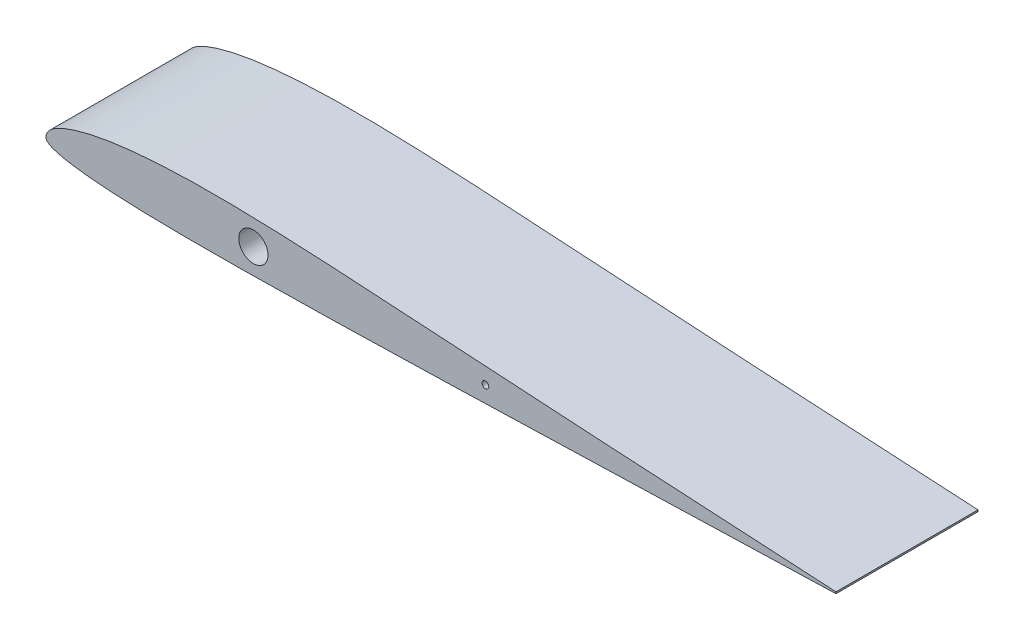
SolidWorks part; units mm, degrees
material "Polyurethane Foam Flexible"
ref_plane "Front Plane" through (0, 0, 0) normal (0, 0, 1) x (1, 0, 0)
ref_plane "Top Plane" through (0, 0, 0) normal (0, 1, 0) x (1, 0, 0)
ref_plane "Right Plane" through (0, 0, 0) normal (1, 0, 0) x (0, 0, -1)
curve "ht32-8-imported"
  spline degree 3 poles (203.2026, 0.2115, 0) (202.75, 0.2358, 0) (201.4822, 0.3036, 0) (199.2299, 0.4276, 0) (196.3046, 0.5865, 0) (192.9787, 0.7694, 0) (189.375, 0.9706, 0) (185.6129, 1.1785, 0) (181.7737, 1.3957, 0) (177.8996, 1.6147, 0) (174.01, 1.8354, 0) (170.1132, 2.0552, 0) (166.2133, 2.2775, 0) (162.3117, 2.4986, 0) (158.4107, 2.722, 0) (154.5106, 2.9441, 0) (150.6142, 3.1678, 0) (146.7204, 3.3936, 0) (142.8309, 3.617, 0) (138.944, 3.8454, 0) (135.0595, 4.0721, 0) (131.1775, 4.3012, 0) (127.2967, 4.5315, 0) (123.4189, 4.7649, 0) (119.5421, 5.0008, 0) (115.6675, 5.2398, 0) (111.7949, 5.4816, 0) (107.9236, 5.7247, 0) (104.0572, 5.9681, 0) (100.1894, 6.212, 0) (96.3188, 6.4543, 0) (92.4477, 6.6946, 0) (88.584, 6.9322, 0) (84.7415, 7.1637, 0) (80.9229, 7.3889, 0) (77.3978, 7.5906, 0) (74.5229, 7.7493, 0) (71.9946, 7.8843, 0) (69.1241, 8.0324, 0) (65.5083, 8.2076, 0) (61.4852, 8.3831, 0) (57.5218, 8.5328, 0) (53.6734, 8.652, 0) (49.9058, 8.739, 0) (46.181, 8.7912, 0) (42.491, 8.8047, 0) (38.8468, 8.7742, 0) (35.2596, 8.6962, 0) (31.7561, 8.5671, 0) (28.3661, 8.3856, 0) (25.1292, 8.152, 0) (22.0798, 7.8688, 0) (19.2587, 7.5428, 0) (16.7019, 7.1837, 0) (14.4336, 6.8058, 0) (12.4541, 6.4216, 0) (10.7471, 6.0418, 0) (9.283, 5.6741, 0) (8.0264, 5.3216, 0) (6.9394, 4.9844, 0) (5.9876, 4.6599, 0) (5.1429, 4.3427, 0) (4.3754, 4.0301, 0) (3.6577, 3.7081, 0) (2.9646, 3.3607, 0) (2.2868, 2.9708, 0) (1.6384, 2.5305, 0) (1.05, 2.0355, 0) (0.5511, 1.4823, 0) (0.1821, 0.8795, 0) (0.0202, 0.3651, 0) (-0.0065, -0.0193, 0) (0.0194, -0.3136, 0) (0.1268, -0.6144, 0) (0.297, -0.8546, 0) (0.4742, -1.036, 0) (0.6922, -1.2054, 0) (0.9846, -1.3848, 0) (1.3525, -1.5668, 0) (1.7794, -1.7448, 0) (2.2605, -1.9172, 0) (2.8067, -2.0876, 0) (3.4413, -2.2602, 0) (4.1881, -2.438, 0) (5.0669, -2.6215, 0) (6.0922, -2.8069, 0) (7.2766, -2.9931, 0) (8.6343, -3.178, 0) (10.1869, -3.3594, 0) (11.9608, -3.5369, 0) (13.9882, -3.7077, 0) (16.2949, -3.8689, 0) (18.8937, -4.0155, 0) (21.7662, -4.1437, 0) (24.8729, -4.2492, 0) (28.1584, -4.3297, 0) (31.5775, -4.3867, 0) (35.0914, -4.4207, 0) (38.6791, -4.4351, 0) (42.3216, -4.4311, 0) (46.0126, -4.4125, 0) (49.7579, -4.3795, 0) (53.5805, -4.3372, 0) (57.5149, -4.2842, 0) (61.5959, -4.2202, 0) (65.8841, -4.1445, 0) (69.584, -4.0721, 0) (72.8088, -4.005, 0) (75.5799, -3.9448, 0) (78.7708, -3.8727, 0) (82.2137, -3.7909, 0) (85.8123, -3.7021, 0) (89.4548, -3.6091, 0) (93.1502, -3.5116, 0) (96.8889, -3.4111, 0) (100.657, -3.3069, 0) (104.4397, -3.2018, 0) (108.2248, -3.0945, 0) (112.0082, -2.9863, 0) (115.791, -2.8766, 0) (119.5782, -2.7658, 0) (123.3765, -2.6523, 0) (127.1945, -2.5376, 0) (131.0416, -2.42, 0) (134.9198, -2.302, 0) (138.8194, -2.1823, 0) (142.7263, -2.0602, 0) (146.6334, -1.9373, 0) (150.5405, -1.8169, 0) (154.4476, -1.6935, 0) (158.3547, -1.5735, 0) (162.2615, -1.4515, 0) (166.1675, -1.3317, 0) (170.0718, -1.2089, 0) (173.9729, -1.0897, 0) (177.8669, -0.9678, 0) (181.7453, -0.8488, 0) (185.5889, -0.7312, 0) (189.3549, -0.6169, 0) (192.9626, -0.5096, 0) (196.292, -0.413, 0) (199.2203, -0.3248, 0) (201.4752, -0.2617, 0) (202.7443, -0.2247, 0) (203.1974, -0.2115, 0) knots 0 0 0 0 0.003316 0.009286 0.0165 0.024744 0.033651 0.0429 0.052304 0.061778 0.071282 0.080801 0.090326 0.099855 0.109385 0.118907 0.128429 0.137932 0.147436 0.156926 0.166412 0.175898 0.185369 0.194848 0.204314 0.213779 0.223243 0.232695 0.242152 0.25158 0.261042 0.270519 0.279949 0.289356 0.298677 0.307928 0.315183 0.319737 0.326448 0.336207 0.346216 0.355902 0.365219 0.374379 0.383467 0.392467 0.401369 0.410123 0.41871 0.427012 0.434953 0.442447 0.449411 0.455723 0.46133 0.466229 0.470471 0.47412 0.47727 0.480016 0.482444 0.484624 0.486615 0.488504 0.490376 0.492284 0.49422 0.496102 0.497896 0.499646 0.501237 0.501776 0.502457 0.503386 0.504071 0.504595 0.505236 0.506086 0.5071 0.508235 0.509467 0.510837 0.512419 0.514277 0.516452 0.518985 0.521897 0.525221 0.529007 0.53333 0.538261 0.543889 0.550243 0.557299 0.56492 0.57298 0.581338 0.589931 0.598683 0.607581 0.616575 0.625681 0.634977 0.644537 0.654462 0.664831 0.675908 0.681531 0.688425 0.696181 0.704877 0.713615 0.722511 0.731528 0.740655 0.749867 0.759101 0.768335 0.777565 0.786786 0.796016 0.805278 0.814581 0.823955 0.833431 0.842961 0.852492 0.862023 0.871554 0.881085 0.890615 0.900146 0.909675 0.9192 0.928718 0.938223 0.947696 0.9571 0.96635 0.975256 0.9835 0.990713 0.996685 1 1 1 1
sketch "Sketch3" plane through (0, 0, 0) normal (0, 0, 1) x (1, 0, 0)
  line L3 (203.2026, 0.2115) -> (203.1974, -0.2115)
  spline S0 degree 3 poles (334.6154, -3985.5649) (434.4726, 3.4305) (316.9129, -6.0481) (199.2299, 0.4276) (196.3046, 0.5865) (192.9787, 0.7694) (189.375, 0.9706) (185.6129, 1.1785) (181.7737, 1.3957) (177.8996, 1.6147) (174.01, 1.8354) (170.1132, 2.0552) (166.2133, 2.2775) (162.3117, 2.4986) (158.4107, 2.722) (154.5106, 2.9441) (150.6142, 3.1678) (146.7204, 3.3936) (142.8309, 3.617) (138.944, 3.8454) (135.0595, 4.0721) (131.1775, 4.3012) (127.2967, 4.5315) (123.4189, 4.7649) (119.5421, 5.0008) (115.6675, 5.2398) (111.7949, 5.4816) (107.9236, 5.7247) (104.0572, 5.9681) (100.1894, 6.212) (96.3188, 6.4543) (92.4477, 6.6946) (88.584, 6.9322) (84.7415, 7.1637) (80.9229, 7.3889) (77.3978, 7.5906) (74.5229, 7.7493) (71.9946, 7.8843) (69.1241, 8.0324) (65.5083, 8.2076) (61.4852, 8.3831) (57.5218, 8.5328) (53.6734, 8.652) (49.9058, 8.739) (46.181, 8.7912) (42.491, 8.8047) (38.8468, 8.7742) (35.2596, 8.6962) (31.7561, 8.5671) (28.3661, 8.3856) (25.1292, 8.152) (22.0798, 7.8688) (19.2587, 7.5428) (16.7019, 7.1837) (14.4336, 6.8058) (12.4541, 6.4216) (10.7471, 6.0418) (9.283, 5.6741) (8.0264, 5.3216) (6.9394, 4.9844) (5.9876, 4.6599) (5.1429, 4.3427) (4.3754, 4.0301) (3.6577, 3.7081) (2.9646, 3.3607) (2.2868, 2.9708) (1.6384, 2.5305) (1.05, 2.0355) (0.5511, 1.4823) (0.1821, 0.8795) (0.0202, 0.3651) (-0.0065, -0.0193) (0.0194, -0.3136) (0.1268, -0.6144) (0.297, -0.8546) (0.4742, -1.036) (0.6922, -1.2054) (0.9846, -1.3848) (1.3525, -1.5668) (1.7794, -1.7448) (2.2605, -1.9172) (2.8067, -2.0876) (3.4413, -2.2602) (4.1881, -2.438) (5.0669, -2.6215) (6.0922, -2.8069) (7.2766, -2.9931) (8.6343, -3.178) (10.1869, -3.3594) (11.9608, -3.5369) (13.9882, -3.7077) (16.2949, -3.8689) (18.8937, -4.0155) (21.7662, -4.1437) (24.8729, -4.2492) (28.1584, -4.3297) (31.5775, -4.3867) (35.0914, -4.4207) (38.6791, -4.4351) (42.3216, -4.4311) (46.0126, -4.4125) (49.7579, -4.3795) (53.5805, -4.3372) (57.5149, -4.2842) (61.5959, -4.2202) (65.8841, -4.1445) (69.584, -4.0721) (72.8088, -4.005) (75.5799, -3.9448) (78.7708, -3.8727) (82.2137, -3.7909) (85.8123, -3.7021) (89.4548, -3.6091) (93.1502, -3.5116) (96.8889, -3.4111) (100.657, -3.3069) (104.4397, -3.2018) (108.2248, -3.0945) (112.0082, -2.9863) (115.791, -2.8766) (119.5782, -2.7658) (123.3765, -2.6523) (127.1945, -2.5376) (131.0416, -2.42) (134.9198, -2.302) (138.8194, -2.1823) (142.7263, -2.0602) (146.6334, -1.9373) (150.5405, -1.8169) (154.4476, -1.6935) (158.3547, -1.5735) (162.2615, -1.4515) (166.1675, -1.3317) (170.0718, -1.2089) (173.9729, -1.0897) (177.8669, -0.9678) (181.7453, -0.8488) (185.5889, -0.7312) (189.3549, -0.6169) (192.9626, -0.5096) (196.292, -0.413) (199.2203, -0.3248) (326.9818, 3.2507) (453.3355, 21.4084) (694.2785, -3955.64) knots -0.845599 -0.845599 -0.845599 -0.845599 0.003316 0.009286 0.0165 0.024744 0.033651 0.0429 0.052304 0.061778 0.071282 0.080801 0.090326 0.099855 0.109385 0.118907 0.128429 0.137932 0.147436 0.156926 0.166412 0.175898 0.185369 0.194848 0.204314 0.213779 0.223243 0.232695 0.242152 0.25158 0.261042 0.270519 0.279949 0.289356 0.298677 0.307928 0.315183 0.319737 0.326448 0.336207 0.346216 0.355902 0.365219 0.374379 0.383467 0.392467 0.401369 0.410123 0.41871 0.427012 0.434953 0.442447 0.449411 0.455723 0.46133 0.466229 0.470471 0.47412 0.47727 0.480016 0.482444 0.484624 0.486615 0.488504 0.490376 0.492284 0.49422 0.496102 0.497896 0.499646 0.501237 0.501776 0.502457 0.503386 0.504071 0.504595 0.505236 0.506086 0.5071 0.508235 0.509467 0.510837 0.512419 0.514277 0.516452 0.518985 0.521897 0.525221 0.529007 0.53333 0.538261 0.543889 0.550243 0.557299 0.56492 0.57298 0.581338 0.589931 0.598683 0.607581 0.616575 0.625681 0.634977 0.644537 0.654462 0.664831 0.675908 0.681531 0.688425 0.696181 0.704877 0.713615 0.722511 0.731528 0.740655 0.749867 0.759101 0.768335 0.777565 0.786786 0.796016 0.805278 0.814581 0.823955 0.833431 0.842961 0.852492 0.862023 0.871554 0.881085 0.890615 0.900146 0.909675 0.9192 0.928718 0.938223 0.947696 0.9571 0.96635 0.975256 0.9835 0.990713 0.996685 1.918381 1.918381 1.918381 1.918381 only from (203.2026, 0.2115) to (203.1974, -0.2115) construction
  spline S1 degree 3 poles (203.2026, 0.2115) (202.75, 0.2358) (201.4822, 0.3036) (199.2299, 0.4276) (196.3046, 0.5865) (192.9787, 0.7694) (189.375, 0.9706) (185.6129, 1.1785) (181.7737, 1.3957) (177.8996, 1.6147) (174.01, 1.8354) (170.1132, 2.0552) (166.2133, 2.2775) (162.3117, 2.4986) (158.4107, 2.722) (154.5106, 2.9441) (150.6142, 3.1678) (146.7204, 3.3936) (142.8309, 3.617) (138.944, 3.8454) (135.0595, 4.0721) (131.1775, 4.3012) (127.2967, 4.5315) (123.4189, 4.7649) (119.5421, 5.0008) (115.6675, 5.2398) (111.7949, 5.4816) (107.9236, 5.7247) (104.0572, 5.9681) (100.1894, 6.212) (96.3188, 6.4543) (92.4477, 6.6946) (88.584, 6.9322) (84.7415, 7.1637) (80.9229, 7.3889) (77.3978, 7.5906) (74.5229, 7.7493) (71.9946, 7.8843) (69.1241, 8.0324) (65.5083, 8.2076) (61.4852, 8.3831) (57.5218, 8.5328) (53.6734, 8.652) (49.9058, 8.739) (46.181, 8.7912) (42.491, 8.8047) (38.8468, 8.7742) (35.2596, 8.6962) (31.7561, 8.5671) (28.3661, 8.3856) (25.1292, 8.152) (22.0798, 7.8688) (19.2587, 7.5428) (16.7019, 7.1837) (14.4336, 6.8058) (12.4541, 6.4216) (10.7471, 6.0418) (9.283, 5.6741) (8.0264, 5.3216) (6.9394, 4.9844) (5.9876, 4.6599) (5.1429, 4.3427) (4.3754, 4.0301) (3.6577, 3.7081) (2.9646, 3.3607) (2.2868, 2.9708) (1.6384, 2.5305) (1.05, 2.0355) (0.5511, 1.4823) (0.1821, 0.8795) (0.0202, 0.3651) (-0.0065, -0.0193) (0.0194, -0.3136) (0.1268, -0.6144) (0.297, -0.8546) (0.4742, -1.036) (0.6922, -1.2054) (0.9846, -1.3848) (1.3525, -1.5668) (1.7794, -1.7448) (2.2605, -1.9172) (2.8067, -2.0876) (3.4413, -2.2602) (4.1881, -2.438) (5.0669, -2.6215) (6.0922, -2.8069) (7.2766, -2.9931) (8.6343, -3.178) (10.1869, -3.3594) (11.9608, -3.5369) (13.9882, -3.7077) (16.2949, -3.8689) (18.8937, -4.0155) (21.7662, -4.1437) (24.8729, -4.2492) (28.1584, -4.3297) (31.5775, -4.3867) (35.0914, -4.4207) (38.6791, -4.4351) (42.3216, -4.4311) (46.0126, -4.4125) (49.7579, -4.3795) (53.5805, -4.3372) (57.5149, -4.2842) (61.5959, -4.2202) (65.8841, -4.1445) (69.584, -4.0721) (72.8088, -4.005) (75.5799, -3.9448) (78.7708, -3.8727) (82.2137, -3.7909) (85.8123, -3.7021) (89.4548, -3.6091) (93.1502, -3.5116) (96.8889, -3.4111) (100.657, -3.3069) (104.4397, -3.2018) (108.2248, -3.0945) (112.0082, -2.9863) (115.791, -2.8766) (119.5782, -2.7658) (123.3765, -2.6523) (127.1945, -2.5376) (131.0416, -2.42) (134.9198, -2.302) (138.8194, -2.1823) (142.7263, -2.0602) (146.6334, -1.9373) (150.5405, -1.8169) (154.4476, -1.6935) (158.3547, -1.5735) (162.2615, -1.4515) (166.1675, -1.3317) (170.0718, -1.2089) (173.9729, -1.0897) (177.8669, -0.9678) (181.7453, -0.8488) (185.5889, -0.7312) (189.3549, -0.6169) (192.9626, -0.5096) (196.292, -0.413) (199.2203, -0.3248) (201.4752, -0.2617) (202.7443, -0.2247) (203.1974, -0.2115) knots 0 0 0 0 0.003316 0.009286 0.0165 0.024744 0.033651 0.0429 0.052304 0.061778 0.071282 0.080801 0.090326 0.099855 0.109385 0.118907 0.128429 0.137932 0.147436 0.156926 0.166412 0.175898 0.185369 0.194848 0.204314 0.213779 0.223243 0.232695 0.242152 0.25158 0.261042 0.270519 0.279949 0.289356 0.298677 0.307928 0.315183 0.319737 0.326448 0.336207 0.346216 0.355902 0.365219 0.374379 0.383467 0.392467 0.401369 0.410123 0.41871 0.427012 0.434953 0.442447 0.449411 0.455723 0.46133 0.466229 0.470471 0.47412 0.47727 0.480016 0.482444 0.484624 0.486615 0.488504 0.490376 0.492284 0.49422 0.496102 0.497896 0.499646 0.501237 0.501776 0.502457 0.503386 0.504071 0.504595 0.505236 0.506086 0.5071 0.508235 0.509467 0.510837 0.512419 0.514277 0.516452 0.518985 0.521897 0.525221 0.529007 0.53333 0.538261 0.543889 0.550243 0.557299 0.56492 0.57298 0.581338 0.589931 0.598683 0.607581 0.616575 0.625681 0.634977 0.644537 0.654462 0.664831 0.675908 0.681531 0.688425 0.696181 0.704877 0.713615 0.722511 0.731528 0.740655 0.749867 0.759101 0.768335 0.777565 0.786786 0.796016 0.805278 0.814581 0.823955 0.833431 0.842961 0.852492 0.862023 0.871554 0.881085 0.890615 0.900146 0.909675 0.9192 0.928718 0.938223 0.947696 0.9571 0.96635 0.975256 0.9835 0.990713 0.996685 1 1 1 1
extrude "Airfoil" add sketch "Sketch3" along normal blind 36.5252
sketch "Sketch8" plane through (0, 0, 0) normal (0, 0, -1) x (-1, 0, 0)
  line L0 (0, 16.6795) -> (0, -1.637) construction
  line L2 (-53.34, 2.1587) -> (-53.34, 8.6559) construction
  line L3 (-53.34, 2.1587) -> (-53.34, -4.3386) construction
  circle A0 centre (-53.34, 2.1587) radius 3.7592
  spline S2 degree 3 poles (-203.2026, 0.2115) (-202.75, 0.2358) (-201.4822, 0.3036) (-199.2299, 0.4276) (-196.3046, 0.5865) (-192.9787, 0.7694) (-189.375, 0.9706) (-185.6129, 1.1785) (-181.7737, 1.3957) (-177.8996, 1.6147) (-174.01, 1.8354) (-170.1132, 2.0552) (-166.2133, 2.2775) (-162.3117, 2.4986) (-158.4107, 2.722) (-154.5106, 2.9441) (-150.6142, 3.1678) (-146.7204, 3.3936) (-142.8309, 3.617) (-138.944, 3.8454) (-135.0595, 4.0721) (-131.1775, 4.3012) (-127.2967, 4.5315) (-123.4189, 4.7649) (-119.5421, 5.0008) (-115.6675, 5.2398) (-111.7949, 5.4816) (-107.9236, 5.7247) (-104.0572, 5.9681) (-100.1894, 6.212) (-96.3188, 6.4543) (-92.4477, 6.6946) (-88.584, 6.9322) (-84.7415, 7.1637) (-80.9229, 7.3889) (-77.3978, 7.5906) (-74.5229, 7.7493) (-71.9946, 7.8843) (-69.1241, 8.0324) (-65.5083, 8.2076) (-61.4852, 8.3831) (-57.5218, 8.5328) (-53.6734, 8.652) (-49.9058, 8.739) (-46.181, 8.7912) (-42.491, 8.8047) (-38.8468, 8.7742) (-35.2596, 8.6962) (-31.7561, 8.5671) (-28.3661, 8.3856) (-25.1292, 8.152) (-22.0798, 7.8688) (-19.2587, 7.5428) (-16.7019, 7.1837) (-14.4336, 6.8058) (-12.4541, 6.4216) (-10.7471, 6.0418) (-9.283, 5.6741) (-8.0264, 5.3216) (-6.9394, 4.9844) (-5.9876, 4.6599) (-5.1429, 4.3427) (-4.3754, 4.0301) (-3.6577, 3.7081) (-2.9646, 3.3607) (-2.2868, 2.9708) (-1.6384, 2.5305) (-1.05, 2.0355) (-0.5511, 1.4823) (-0.1821, 0.8795) (-0.0202, 0.3651) (0.0065, -0.0193) (-0.0194, -0.3136) (-0.1268, -0.6144) (-0.297, -0.8546) (-0.4742, -1.036) (-0.6922, -1.2054) (-0.9846, -1.3848) (-1.3525, -1.5668) (-1.7794, -1.7448) (-2.2605, -1.9172) (-2.8067, -2.0876) (-3.4413, -2.2602) (-4.1881, -2.438) (-5.0669, -2.6215) (-6.0922, -2.8069) (-7.2766, -2.9931) (-8.6343, -3.178) (-10.1869, -3.3594) (-11.9608, -3.5369) (-13.9882, -3.7077) (-16.2949, -3.8689) (-18.8937, -4.0155) (-21.7662, -4.1437) (-24.8729, -4.2492) (-28.1584, -4.3297) (-31.5775, -4.3867) (-35.0914, -4.4207) (-38.6791, -4.4351) (-42.3216, -4.4311) (-46.0126, -4.4125) (-49.7579, -4.3795) (-53.5805, -4.3372) (-57.5149, -4.2842) (-61.5959, -4.2202) (-65.8841, -4.1445) (-69.584, -4.0721) (-72.8088, -4.005) (-75.5799, -3.9448) (-78.7708, -3.8727) (-82.2137, -3.7909) (-85.8123, -3.7021) (-89.4548, -3.6091) (-93.1502, -3.5116) (-96.8889, -3.4111) (-100.657, -3.3069) (-104.4397, -3.2018) (-108.2248, -3.0945) (-112.0082, -2.9863) (-115.791, -2.8766) (-119.5782, -2.7658) (-123.3765, -2.6523) (-127.1945, -2.5376) (-131.0416, -2.42) (-134.9198, -2.302) (-138.8194, -2.1823) (-142.7263, -2.0602) (-146.6334, -1.9373) (-150.5405, -1.8169) (-154.4476, -1.6935) (-158.3547, -1.5735) (-162.2615, -1.4515) (-166.1675, -1.3317) (-170.0718, -1.2089) (-173.9729, -1.0897) (-177.8669, -0.9678) (-181.7453, -0.8488) (-185.5889, -0.7312) (-189.3549, -0.6169) (-192.9626, -0.5096) (-196.292, -0.413) (-199.2203, -0.3248) (-201.4752, -0.2617) (-202.7443, -0.2247) (-203.1974, -0.2115) knots 0 0 0 0 0.003316 0.009286 0.0165 0.024744 0.033651 0.0429 0.052304 0.061778 0.071282 0.080801 0.090326 0.099855 0.109385 0.118907 0.128429 0.137932 0.147436 0.156926 0.166412 0.175898 0.185369 0.194848 0.204314 0.213779 0.223243 0.232695 0.242152 0.25158 0.261042 0.270519 0.279949 0.289356 0.298677 0.307928 0.315183 0.319737 0.326448 0.336207 0.346216 0.355902 0.365219 0.374379 0.383467 0.392467 0.401369 0.410123 0.41871 0.427012 0.434953 0.442447 0.449411 0.455723 0.46133 0.466229 0.470471 0.47412 0.47727 0.480016 0.482444 0.484624 0.486615 0.488504 0.490376 0.492284 0.49422 0.496102 0.497896 0.499646 0.501237 0.501776 0.502457 0.503386 0.504071 0.504595 0.505236 0.506086 0.5071 0.508235 0.509467 0.510837 0.512419 0.514277 0.516452 0.518985 0.521897 0.525221 0.529007 0.53333 0.538261 0.543889 0.550243 0.557299 0.56492 0.57298 0.581338 0.589931 0.598683 0.607581 0.616575 0.625681 0.634977 0.644537 0.654462 0.664831 0.675908 0.681531 0.688425 0.696181 0.704877 0.713615 0.722511 0.731528 0.740655 0.749867 0.759101 0.768335 0.777565 0.786786 0.796016 0.805278 0.814581 0.823955 0.833431 0.842961 0.852492 0.862023 0.871554 0.881085 0.890615 0.900146 0.909675 0.9192 0.928718 0.938223 0.947696 0.9571 0.96635 0.975256 0.9835 0.990713 0.996685 1 1 1 1 construction
  dimension "D1" = 7.5184
  dimension "D2" = 53.34
extrude "Camera Channel" cut sketch "Sketch8" against normal up to next
sketch "Sketch9" plane through (0, 0, 0) normal (0, 0, -1) x (-1, 0, 0)
  line L0 (-113.03, 2.0876) -> (-113.03, 5.4046) construction
  line L1 (-113.03, 0.3604) -> (-113.03, -2.9566) construction
  circle A0 centre (-113.03, 1.224) radius 0.8636
  circle A1 centre (-53.34, 2.1587) radius 3.7592 construction
  spline S0 degree 3 poles (-370.7177, -1986.1352) (-386.1593, 0.2045) (-292.9152, -4.7275) (-199.2299, 0.4276) (-196.3046, 0.5865) (-192.9787, 0.7694) (-189.375, 0.9706) (-185.6129, 1.1785) (-181.7737, 1.3957) (-177.8996, 1.6147) (-174.01, 1.8354) (-170.1132, 2.0552) (-166.2133, 2.2775) (-162.3117, 2.4986) (-158.4107, 2.722) (-154.5106, 2.9441) (-150.6142, 3.1678) (-146.7204, 3.3936) (-142.8309, 3.617) (-138.944, 3.8454) (-135.0595, 4.0721) (-131.1775, 4.3012) (-127.2967, 4.5315) (-123.4189, 4.7649) (-119.5421, 5.0008) (-115.6675, 5.2398) (-111.7949, 5.4816) (-107.9236, 5.7247) (-104.0572, 5.9681) (-100.1894, 6.212) (-96.3188, 6.4543) (-92.4477, 6.6946) (-88.584, 6.9322) (-84.7415, 7.1637) (-80.9229, 7.3889) (-77.3978, 7.5906) (-74.5229, 7.7493) (-71.9946, 7.8843) (-69.1241, 8.0324) (-65.5083, 8.2076) (-61.4852, 8.3831) (-57.5218, 8.5328) (-53.6734, 8.652) (-49.9058, 8.739) (-46.181, 8.7912) (-42.491, 8.8047) (-38.8468, 8.7742) (-35.2596, 8.6962) (-31.7561, 8.5671) (-28.3661, 8.3856) (-25.1292, 8.152) (-22.0798, 7.8688) (-19.2587, 7.5428) (-16.7019, 7.1837) (-14.4336, 6.8058) (-12.4541, 6.4216) (-10.7471, 6.0418) (-9.283, 5.6741) (-8.0264, 5.3216) (-6.9394, 4.9844) (-5.9876, 4.6599) (-5.1429, 4.3427) (-4.3754, 4.0301) (-3.6577, 3.7081) (-2.9646, 3.3607) (-2.2868, 2.9708) (-1.6384, 2.5305) (-1.05, 2.0355) (-0.5511, 1.4823) (-0.1821, 0.8795) (-0.0202, 0.3651) (0.0065, -0.0193) (-0.0194, -0.3136) (-0.1268, -0.6144) (-0.297, -0.8546) (-0.4742, -1.036) (-0.6922, -1.2054) (-0.9846, -1.3848) (-1.3525, -1.5668) (-1.7794, -1.7448) (-2.2605, -1.9172) (-2.8067, -2.0876) (-3.4413, -2.2602) (-4.1881, -2.438) (-5.0669, -2.6215) (-6.0922, -2.8069) (-7.2766, -2.9931) (-8.6343, -3.178) (-10.1869, -3.3594) (-11.9608, -3.5369) (-13.9882, -3.7077) (-16.2949, -3.8689) (-18.8937, -4.0155) (-21.7662, -4.1437) (-24.8729, -4.2492) (-28.1584, -4.3297) (-31.5775, -4.3867) (-35.0914, -4.4207) (-38.6791, -4.4351) (-42.3216, -4.4311) (-46.0126, -4.4125) (-49.7579, -4.3795) (-53.5805, -4.3372) (-57.5149, -4.2842) (-61.5959, -4.2202) (-65.8841, -4.1445) (-69.584, -4.0721) (-72.8088, -4.005) (-75.5799, -3.9448) (-78.7708, -3.8727) (-82.2137, -3.7909) (-85.8123, -3.7021) (-89.4548, -3.6091) (-93.1502, -3.5116) (-96.8889, -3.4111) (-100.657, -3.3069) (-104.4397, -3.2018) (-108.2248, -3.0945) (-112.0082, -2.9863) (-115.791, -2.8766) (-119.5782, -2.7658) (-123.3765, -2.6523) (-127.1945, -2.5376) (-131.0416, -2.42) (-134.9198, -2.302) (-138.8194, -2.1823) (-142.7263, -2.0602) (-146.6334, -1.9373) (-150.5405, -1.8169) (-154.4476, -1.6935) (-158.3547, -1.5735) (-162.2615, -1.4515) (-166.1675, -1.3317) (-170.0718, -1.2089) (-173.9729, -1.0897) (-177.8669, -0.9678) (-181.7453, -0.8488) (-185.5889, -0.7312) (-189.3549, -0.6169) (-192.9626, -0.5096) (-196.292, -0.413) (-199.2203, -0.3248) (-300.851, 2.5194) (-401.2299, 14.5438) (-558.1905, -1960.49) knots -0.669801 -0.669801 -0.669801 -0.669801 0.003316 0.009286 0.0165 0.024744 0.033651 0.0429 0.052304 0.061778 0.071282 0.080801 0.090326 0.099855 0.109385 0.118907 0.128429 0.137932 0.147436 0.156926 0.166412 0.175898 0.185369 0.194848 0.204314 0.213779 0.223243 0.232695 0.242152 0.25158 0.261042 0.270519 0.279949 0.289356 0.298677 0.307928 0.315183 0.319737 0.326448 0.336207 0.346216 0.355902 0.365219 0.374379 0.383467 0.392467 0.401369 0.410123 0.41871 0.427012 0.434953 0.442447 0.449411 0.455723 0.46133 0.466229 0.470471 0.47412 0.47727 0.480016 0.482444 0.484624 0.486615 0.488504 0.490376 0.492284 0.49422 0.496102 0.497896 0.499646 0.501237 0.501776 0.502457 0.503386 0.504071 0.504595 0.505236 0.506086 0.5071 0.508235 0.509467 0.510837 0.512419 0.514277 0.516452 0.518985 0.521897 0.525221 0.529007 0.53333 0.538261 0.543889 0.550243 0.557299 0.56492 0.57298 0.581338 0.589931 0.598683 0.607581 0.616575 0.625681 0.634977 0.644537 0.654462 0.664831 0.675908 0.681531 0.688425 0.696181 0.704877 0.713615 0.722511 0.731528 0.740655 0.749867 0.759101 0.768335 0.777565 0.786786 0.796016 0.805278 0.814581 0.823955 0.833431 0.842961 0.852492 0.862023 0.871554 0.881085 0.890615 0.900146 0.909675 0.9192 0.928718 0.938223 0.947696 0.9571 0.96635 0.975256 0.9835 0.990713 0.996685 1.727171 1.727171 1.727171 1.727171 only from (-203.2026, 0.2115) to (-203.1974, -0.2115) construction
  spline S1 degree 3 poles (-203.2026, 0.2115) (-202.75, 0.2358) (-201.4822, 0.3036) (-199.2299, 0.4276) (-196.3046, 0.5865) (-192.9787, 0.7694) (-189.375, 0.9706) (-185.6129, 1.1785) (-181.7737, 1.3957) (-177.8996, 1.6147) (-174.01, 1.8354) (-170.1132, 2.0552) (-166.2133, 2.2775) (-162.3117, 2.4986) (-158.4107, 2.722) (-154.5106, 2.9441) (-150.6142, 3.1678) (-146.7204, 3.3936) (-142.8309, 3.617) (-138.944, 3.8454) (-135.0595, 4.0721) (-131.1775, 4.3012) (-127.2967, 4.5315) (-123.4189, 4.7649) (-119.5421, 5.0008) (-115.6675, 5.2398) (-111.7949, 5.4816) (-107.9236, 5.7247) (-104.0572, 5.9681) (-100.1894, 6.212) (-96.3188, 6.4543) (-92.4477, 6.6946) (-88.584, 6.9322) (-84.7415, 7.1637) (-80.9229, 7.3889) (-77.3978, 7.5906) (-74.5229, 7.7493) (-71.9946, 7.8843) (-69.1241, 8.0324) (-65.5083, 8.2076) (-61.4852, 8.3831) (-57.5218, 8.5328) (-53.6734, 8.652) (-49.9058, 8.739) (-46.181, 8.7912) (-42.491, 8.8047) (-38.8468, 8.7742) (-35.2596, 8.6962) (-31.7561, 8.5671) (-28.3661, 8.3856) (-25.1292, 8.152) (-22.0798, 7.8688) (-19.2587, 7.5428) (-16.7019, 7.1837) (-14.4336, 6.8058) (-12.4541, 6.4216) (-10.7471, 6.0418) (-9.283, 5.6741) (-8.0264, 5.3216) (-6.9394, 4.9844) (-5.9876, 4.6599) (-5.1429, 4.3427) (-4.3754, 4.0301) (-3.6577, 3.7081) (-2.9646, 3.3607) (-2.2868, 2.9708) (-1.6384, 2.5305) (-1.05, 2.0355) (-0.5511, 1.4823) (-0.1821, 0.8795) (-0.0202, 0.3651) (0.0065, -0.0193) (-0.0194, -0.3136) (-0.1268, -0.6144) (-0.297, -0.8546) (-0.4742, -1.036) (-0.6922, -1.2054) (-0.9846, -1.3848) (-1.3525, -1.5668) (-1.7794, -1.7448) (-2.2605, -1.9172) (-2.8067, -2.0876) (-3.4413, -2.2602) (-4.1881, -2.438) (-5.0669, -2.6215) (-6.0922, -2.8069) (-7.2766, -2.9931) (-8.6343, -3.178) (-10.1869, -3.3594) (-11.9608, -3.5369) (-13.9882, -3.7077) (-16.2949, -3.8689) (-18.8937, -4.0155) (-21.7662, -4.1437) (-24.8729, -4.2492) (-28.1584, -4.3297) (-31.5775, -4.3867) (-35.0914, -4.4207) (-38.6791, -4.4351) (-42.3216, -4.4311) (-46.0126, -4.4125) (-49.7579, -4.3795) (-53.5805, -4.3372) (-57.5149, -4.2842) (-61.5959, -4.2202) (-65.8841, -4.1445) (-69.584, -4.0721) (-72.8088, -4.005) (-75.5799, -3.9448) (-78.7708, -3.8727) (-82.2137, -3.7909) (-85.8123, -3.7021) (-89.4548, -3.6091) (-93.1502, -3.5116) (-96.8889, -3.4111) (-100.657, -3.3069) (-104.4397, -3.2018) (-108.2248, -3.0945) (-112.0082, -2.9863) (-115.791, -2.8766) (-119.5782, -2.7658) (-123.3765, -2.6523) (-127.1945, -2.5376) (-131.0416, -2.42) (-134.9198, -2.302) (-138.8194, -2.1823) (-142.7263, -2.0602) (-146.6334, -1.9373) (-150.5405, -1.8169) (-154.4476, -1.6935) (-158.3547, -1.5735) (-162.2615, -1.4515) (-166.1675, -1.3317) (-170.0718, -1.2089) (-173.9729, -1.0897) (-177.8669, -0.9678) (-181.7453, -0.8488) (-185.5889, -0.7312) (-189.3549, -0.6169) (-192.9626, -0.5096) (-196.292, -0.413) (-199.2203, -0.3248) (-201.4752, -0.2617) (-202.7443, -0.2247) (-203.1974, -0.2115) knots 0 0 0 0 0.003316 0.009286 0.0165 0.024744 0.033651 0.0429 0.052304 0.061778 0.071282 0.080801 0.090326 0.099855 0.109385 0.118907 0.128429 0.137932 0.147436 0.156926 0.166412 0.175898 0.185369 0.194848 0.204314 0.213779 0.223243 0.232695 0.242152 0.25158 0.261042 0.270519 0.279949 0.289356 0.298677 0.307928 0.315183 0.319737 0.326448 0.336207 0.346216 0.355902 0.365219 0.374379 0.383467 0.392467 0.401369 0.410123 0.41871 0.427012 0.434953 0.442447 0.449411 0.455723 0.46133 0.466229 0.470471 0.47412 0.47727 0.480016 0.482444 0.484624 0.486615 0.488504 0.490376 0.492284 0.49422 0.496102 0.497896 0.499646 0.501237 0.501776 0.502457 0.503386 0.504071 0.504595 0.505236 0.506086 0.5071 0.508235 0.509467 0.510837 0.512419 0.514277 0.516452 0.518985 0.521897 0.525221 0.529007 0.53333 0.538261 0.543889 0.550243 0.557299 0.56492 0.57298 0.581338 0.589931 0.598683 0.607581 0.616575 0.625681 0.634977 0.644537 0.654462 0.664831 0.675908 0.681531 0.688425 0.696181 0.704877 0.713615 0.722511 0.731528 0.740655 0.749867 0.759101 0.768335 0.777565 0.786786 0.796016 0.805278 0.814581 0.823955 0.833431 0.842961 0.852492 0.862023 0.871554 0.881085 0.890615 0.900146 0.909675 0.9192 0.928718 0.938223 0.947696 0.9571 0.96635 0.975256 0.9835 0.990713 0.996685 1 1 1 1 construction
  dimension "D2" = 1.7272
  dimension "D1" = 59.69
extrude "Cut-Extrude1" cut sketch "Sketch9" against normal through all
